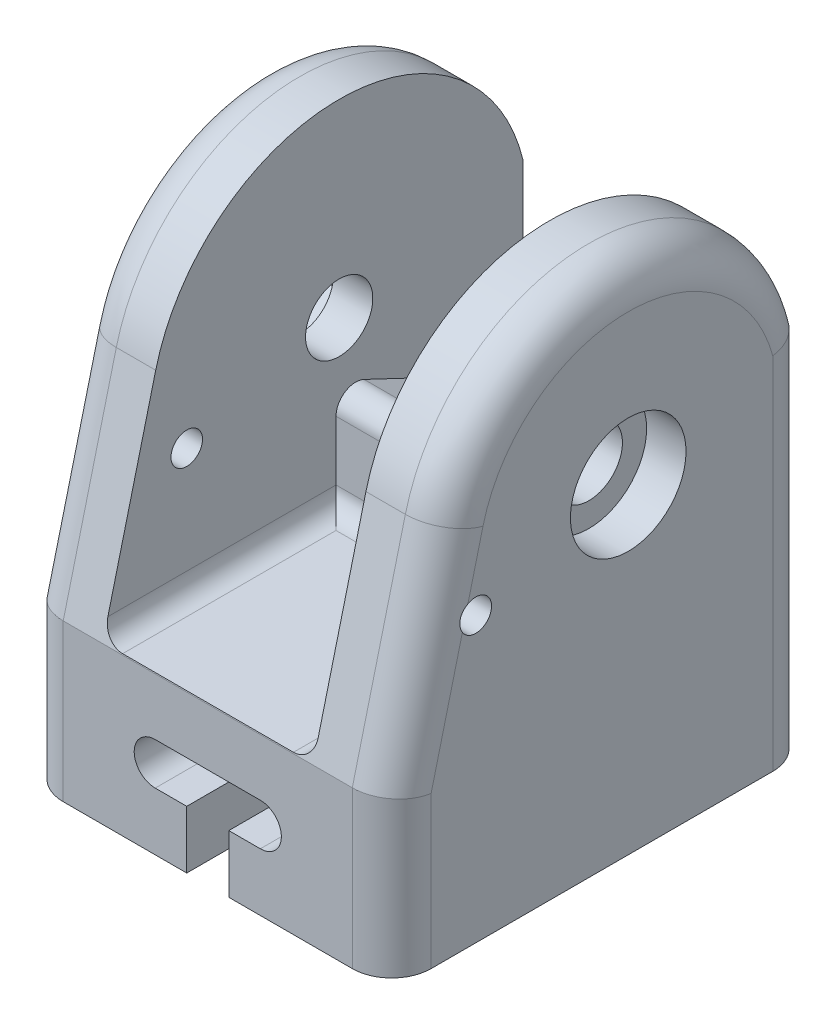
SolidWorks part; units mm, degrees
ref_plane "Front Plane" through (0, 0, 0) normal (0, 0, 1) x (1, 0, 0)
ref_plane "Top Plane" through (0, 0, 0) normal (0, 1, 0) x (1, 0, 0)
ref_plane "Right Plane" through (0, 0, 0) normal (1, 0, 0) x (0, 0, -1)
sketch "Sketch2" plane through (0, 0, 0) normal (0, 1, 0) x (1, 0, 0)
  line L0 (5, 10) -> (8.75, 10)
  line L1 (-8.75, -10) -> (8.75, -10)
  line L2 (-8.75, -10) -> (-8.75, 10)
  line L3 (-8.75, 10) -> (-5, 10)
  line L4 (8.75, -10) -> (8.75, 10)
  line L5 (-8.75, -10) -> (8.75, 10) construction
  line L6 (-8.75, 10) -> (8.75, -10) construction
  line L8 (-5, 10) -> (-5, 5)
  line L9 (-5, 5) -> (5, 5)
  line L10 (5, 10) -> (5, 5)
  point P0 (0, 0)
  point P15 (-5, 5)
  dimension "D1" = 17.5
  dimension "D2" = 20
  dimension "D3" = 3.75
  dimension "D4" = 5
extrude "Boss-Extrude1" add sketch "Sketch2" along normal blind 22.5
sketch "Sketch3" plane through (0, 22.5, 0) normal (0, 1, 0) x (1, 0, 0)
  line L0 (-8.75, -10) -> (8.75, -10) construction
  line L1 (-5, 10) -> (5, 10)
  line L2 (-5, 10) -> (-5, -10)
  line L3 (-5, -10) -> (5, -10)
  line L4 (5, 10) -> (5, -10)
  line L5 (5, 10) -> (5, 5) construction
extrude "Cut-Extrude1" cut sketch "Sketch3" against normal blind 17.5
sketch "Sketch4" plane through (8.75, 0, 0) normal (1, 0, 0) x (0, 0, -1)
  line L0 (10, 22.5) -> (10, 0) construction
  line L1 (-10, 22.5) -> (10, 22.5) construction
  line L2 (10, 14.8565) -> (10, 0)
  line L3 (10, 0) -> (-10, 0)
  line L4 (-10, 0) -> (-10, 4.9522)
  line L6 (-10, 4.9522) -> (-7.4764, 14.9522)
  line L7 (-10, 22.5) -> (-10, 0) construction
  circle A0 centre (1.25, 12.75) radius 1.6
  arc A1 (10, 14.8565) -> (-7.4764, 14.9522) centre (1.25, 12.75) ccw
  circle A2 centre (-6, 11) radius 0.75
  dimension "D1" = 8.75
  dimension "D4" = 3.2
  dimension "D7" = 9
  dimension "D6" = 1.75
  dimension "D8" = 1.5
  dimension "D2" = 9.75
  dimension "D3" = 10
  dimension "D5" = 4
extrude "Cut-Extrude2" cut sketch "Sketch4" against normal through all flip side to cut
fillet "Fillet1" radius 1.875 8 edges at (-8.75, 9.9522, 8.7382) (8.75, 9.9522, 8.7382) (-8.75, 7.4283, -10) (8.75, 7.4283, -10) (-8.75, 2.4761, 10) (8.75, 2.4761, 10) (-8.75, 21.7499, -1.2993) (8.75, 21.7499, -1.2993)
sketch "Sketch7" plane through (8.75, 0, 0) normal (1, 0, 0) x (0, 0, -1)
  line L1 (-10, 0) -> (10, 0)
  line L2 (-10, 0) -> (-10, 25)
  line L3 (-10, 25) -> (10, 25)
  line L4 (10, 0) -> (10, 25)
  dimension "D1" = 25
  dimension "D2" = 20
extrude "Cut-Extrude4" cut sketch "Sketch7" against normal blind 8.75
sketch "Sketch8" plane through (-5, 0, 0) normal (1, 0, 0) x (0, 0, -1)
  line L0 (5, 5) -> (5, 8.4)
  line L2 (5, 8.4) -> (1.1, 10.25)
  line L3 (1.1, 10.25) -> (1.1, 5)
  line L4 (5, 5) -> (-9.9879, 5) construction
  line L5 (1.1, 5) -> (5, 5)
  line L7 (5, 5) -> (5, 0) construction
  dimension "D1" = 3.4
  dimension "D2" = 5.25
  dimension "D3" = 3.9
extrude "Boss-Extrude3" add sketch "Sketch8" along normal up to surface (5 mm away) up to face at (0, 2.9904, 3.9976)
fillet "Fillet2" radius 0.9375 4 edges at (-2.5, 8.4, -5) (-2.5, 10.25, -1.1) (-2.5, 5, -1.1) (-5, 5, 4.444)
mirror "Mirror2" about plane through (0, 0, 0) normal (-1, 0, 0) of bodies 108
sketch "Sketch11" plane through (8.75, 0, 0) normal (1, 0, 0) x (0, 0, -1)
  circle A0 centre (1.25, 12.75) radius 2.75
  dimension "D1" = 5.5
extrude "Cut-Extrude6" cut sketch "Sketch11" against normal blind 1.875
sketch "Sketch12" plane through (-8.75, 0, 0) normal (-1, 0, 0) x (0, 0, 1)
  line L1 (-1.25, 15.9254) -> (-4, 14.3377)
  line L2 (-4, 14.3377) -> (-4, 11.1623)
  line L3 (-4, 11.1623) -> (-1.25, 9.5746)
  line L4 (-1.25, 9.5746) -> (1.5, 11.1623)
  line L5 (1.5, 11.1623) -> (1.5, 14.3377)
  line L6 (1.5, 14.3377) -> (-1.25, 15.9254)
  circle A0 centre (-1.25, 12.75) radius 2.75 construction
  dimension "D1" = 5.5
extrude "Cut-Extrude7" cut sketch "Sketch12" against normal blind 1.875
sketch "Sketch13" [suppressed] plane through (-8.75, 0, 0) normal (-1, 0, 0) x (0, 0, 1)
  text T0 "I" font "Century Schoolbook" height in points 36
extrude "Boss-Extrude4" [suppressed] add sketch "Sketch13" along normal blind 0.2
sketch "Sketch14" plane through (-8.75, 0, 0) normal (-1, 0, 0) x (0, 0, 1)
  text T0 "M" font "Century Schoolbook" height in points 36
extrude "Boss-Extrude5" [suppressed] add sketch "Sketch14" along normal blind 0.2
sketch "Sketch16" plane through (-8.75, 0, 0) normal (-1, 0, 0) x (0, 0, 1)
  text T0 "R" font "Century Schoolbook" height in points 36
extrude "Boss-Extrude6" [suppressed] add sketch "Sketch16" along normal blind 0.2
sketch "Sketch17" plane through (-8.75, 0, 0) normal (-1, 0, 0) x (0, 0, 1)
  text T0 "P" font "Century Schoolbook" height in points 36
extrude "Boss-Extrude7" [suppressed] add sketch "Sketch17" along normal blind 0.2
sketch "Sketch18" plane through (-8.75, 0, 0) normal (-1, 0, 0) x (0, 0, 1)
  text T0 "T" font "Century Schoolbook" height in points 36
extrude "Boss-Extrude8" add sketch "Sketch18" along normal blind 0.2
sketch "Sketch19" plane through (0, 0, 0) normal (0, -1, 0) x (1, 0, 0)
  line L0 (-8.75, 2.1695) -> (-8.75, -2.0489)
  line L12 (-5, -5) -> (5, -5)
  line L13 (5, -5) -> (5, -10)
  line L14 (5, -10) -> (6.875, -10)
  line L15 (8.75, -8.125) -> (8.75, 8.125)
  line L16 (6.875, 10) -> (-6.875, 10)
  line L17 (-8.75, 8.125) -> (-8.75, 2.1695)
  line L18 (-8.75, 2.1695) -> (-8.95, 2.1695)
  line L19 (-8.75, 2.1695) -> (-8.95, 2.1695)
  line L20 (-8.95, 2.1695) -> (-8.95, -2.0489)
  line L21 (-8.75, -2.0489) -> (-8.75, -8.125)
  line L22 (-6.875, -10) -> (-5, -10)
  line L23 (-5, -10) -> (-5, -5)
  line L24 (-5, -5) -> (5, -5)
  line L25 (5, -5) -> (5, -10)
  line L26 (5, -10) -> (6.875, -10)
  line L27 (8.75, -8.125) -> (8.75, 8.125)
  line L28 (6.875, 10) -> (-6.875, 10)
  line L29 (-8.75, 8.125) -> (-8.75, 2.1695)
  line L33 (-8.75, -2.0489) -> (-8.75, -8.125)
  line L34 (-6.875, -10) -> (-5, -10)
  line L35 (-5, -10) -> (-5, -5)
  line L37 (-8.95, 2.1695) -> (-8.95, -2.0489)
  line L38 (-8.95, -2.0489) -> (-8.75, -2.0489)
  line L39 (-8.95, -2.0489) -> (-8.75, -2.0489)
  arc A4 (6.875, -10) -> (8.75, -8.125) centre (6.875, -8.125) ccw
  arc A5 (8.75, 8.125) -> (6.875, 10) centre (6.875, 8.125) ccw
  arc A6 (-6.875, 10) -> (-8.75, 8.125) centre (-6.875, 8.125) ccw
  arc A7 (-8.75, -8.125) -> (-6.875, -10) centre (-6.875, -8.125) ccw
  arc A8 (6.875, -10) -> (8.75, -8.125) centre (6.875, -8.125) ccw
  arc A9 (8.75, 8.125) -> (6.875, 10) centre (6.875, 8.125) ccw
  arc A10 (-6.875, 10) -> (-8.75, 8.125) centre (-6.875, 8.125) ccw
  arc A11 (-8.75, -8.125) -> (-6.875, -10) centre (-6.875, -8.125) ccw
  line M17 (-5, -5) -> (5, -5)
  line M18 (5, -5) -> (5, -10)
  line M19 (5, -10) -> (6.875, -10)
  arc M20 (6.875, -10) -> (8.75, -8.125) centre (6.875, -8.125) ccw
  line M21 (8.75, -8.125) -> (8.75, 8.125)
  arc M22 (8.75, 8.125) -> (6.875, 10) centre (6.875, 8.125) ccw
  line M23 (6.875, 10) -> (-6.875, 10)
  arc M24 (-6.875, 10) -> (-8.75, 8.125) centre (-6.875, 8.125) ccw
  line M25 (-8.75, 8.125) -> (-8.75, 2.1695)
  line M29 (-8.75, -2.0489) -> (-8.75, -8.125)
  arc M30 (-8.75, -8.125) -> (-6.875, -10) centre (-6.875, -8.125) ccw
  line M31 (-6.875, -10) -> (-5, -10)
  line M32 (-5, -10) -> (-5, -5)
  dimension "D1" = 0
extrude "Boss-Extrude9" add sketch "Sketch19" along normal blind 2.5 contours L0 M29 M30 M31 M32 M17 M18 M19 M20 M21 M22 M23 M24 M25 region at (0, 0, 1.2627)
sketch "Sketch20" plane through (0, 0, -5) normal (0, 0, -1) x (-1, 0, 0)
  line L0 (1, 0.25) -> (2.5, 0.25)
  line L1 (5, 7.8071) -> (5, -2.5) construction
  line L6 (-2.5, 1.25) -> (2.5, 1.25) construction
  line L7 (-2.5, 2.25) -> (2.5, 2.25)
  line L8 (-2.5, 0.25) -> (-1, 0.25)
  line L9 (0, 1.25) -> (0, -2.5) construction
  line L10 (1, 0.25) -> (1, -2.5)
  line L11 (-1, 0.25) -> (-1, -2.5)
  line L12 (5, 7.8071) -> (-5, 7.8071) construction
  arc A2 (-2.5, 2.25) -> (-2.5, 0.25) centre (-2.5, 1.25) ccw
  arc A3 (2.5, 0.25) -> (2.5, 2.25) centre (2.5, 1.25) ccw
  arc A5 (-1, -2.5) -> (1, -2.5) centre (0, -2.5) ccw
  point P5 (0, 1.25)
  point P8 (0, 1.25)
  point P14 (0, -0.625)
  dimension "D1" = 3.75
  dimension "D2" = 1
  dimension "D3" = 5
  dimension "D4" = 6.5571
extrude "Cut-Extrude8" cut sketch "Sketch20" against normal through all
